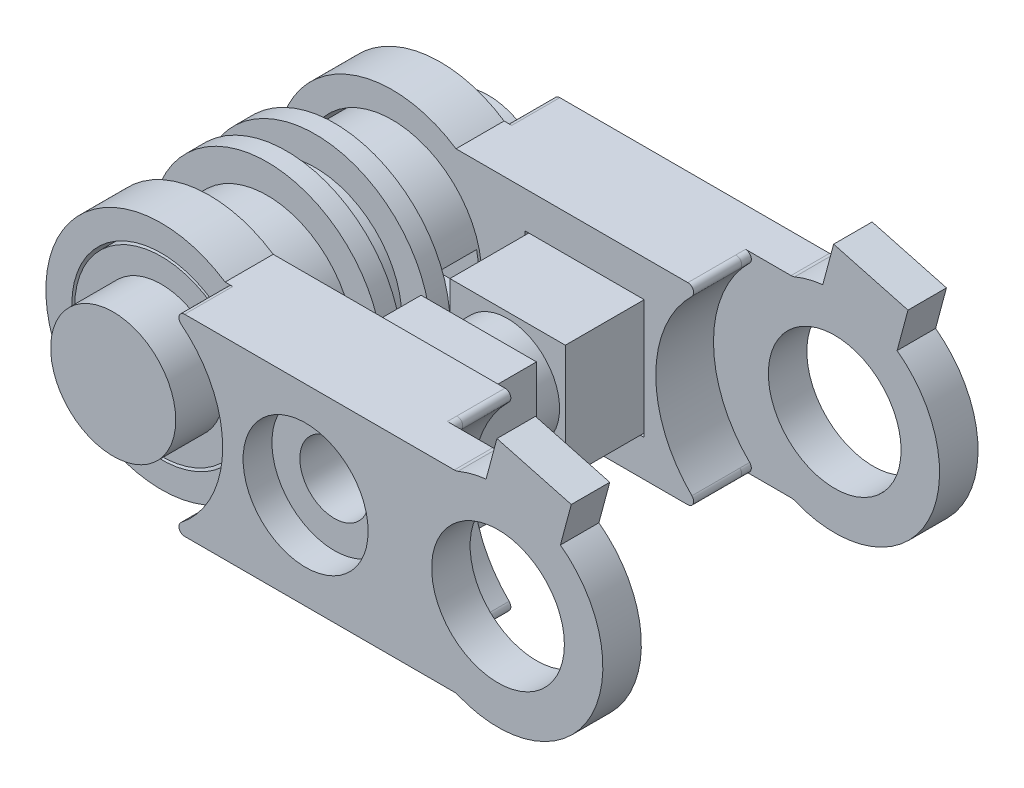
SolidWorks part; units mm, degrees
material "ABS"
ref_plane "正面" through (0, 0, 0) normal (0, 0, 1) x (1, 0, 0)
ref_plane "平面" through (0, 0, 0) normal (0, 1, 0) x (1, 0, 0)
ref_plane "右側面" through (0, 0, 0) normal (1, 0, 0) x (0, 0, -1)
sketch "ｽｹｯﾁ1" plane through (0, 0, 0) normal (0, 0, 1) x (1, 0, 0)
  circle A0 centre (0, 0) radius 4.5
  dimension "D1" = 9
extrude "ﾎﾞｽ - 押し出し1" add sketch "ｽｹｯﾁ1" along normal blind 3
sketch "ｽｹｯﾁ2" plane through (0, 0, 0) normal (0, 0, -1) x (-1, 0, 0)
  circle A0 centre (0, 0) radius 6
  dimension "D1" = 12
extrude "ﾎﾞｽ - 押し出し2" add sketch "ｽｹｯﾁ2" along normal blind 1
sketch "ｽｹｯﾁ3" plane through (0, 0, -1) normal (0, 0, -1) x (-1, 0, 0)
  circle A0 centre (0, 0) radius 4.5 construction
  circle A1 centre (0, 0) radius 4.5
extrude "ﾎﾞｽ - 押し出し3" add sketch "ｽｹｯﾁ3" along normal blind 1.5
sketch "ｽｹｯﾁ4" plane through (0, 0, -2.5) normal (0, 0, -1) x (-1, 0, 0)
  circle A1 centre (0, 0) radius 6
  circle A2 centre (0, 0) radius 6
  dimension "D1" = 0
extrude "ﾎﾞｽ - 押し出し4" add sketch "ｽｹｯﾁ4" along normal blind 1
sketch "ｽｹｯﾁ5" plane through (0, 0, -3.5) normal (0, 0, -1) x (-1, 0, 0)
  circle A0 centre (0, 0) radius 4.5 construction
  circle A1 centre (0, 0) radius 4.5
extrude "ﾎﾞｽ - 押し出し5" add sketch "ｽｹｯﾁ5" along normal blind 3
sketch "ｽｹｯﾁ6" plane through (0, 0, -6.5) normal (0, 0, -1) x (-1, 0, 0)
  circle A1 centre (0, 0) radius 6
  circle A2 centre (0, 0) radius 6
  dimension "D1" = 0
extrude "ﾎﾞｽ - 押し出し6" add sketch "ｽｹｯﾁ6" along normal blind 1
sketch "ｽｹｯﾁ7" plane through (0, 0, 3) normal (0, 0, 1) x (1, 0, 0)
  circle A1 centre (0, 0) radius 6
  circle A2 centre (0, 0) radius 6
  dimension "D1" = 0
extrude "ﾎﾞｽ - 押し出し7" add sketch "ｽｹｯﾁ7" along normal blind 1
sketch "ｽｹｯﾁ10" plane through (0, 0, 4) normal (0, 0, 1) x (1, 0, 0)
  line L1 (3.5, -3.5) -> (-3.5, -3.5) construction
  line L2 (3.5, -3.5) -> (3.5, 3.5) construction
  line L3 (3.5, 3.5) -> (-3.5, 3.5) construction
  line L4 (-3.5, -3.5) -> (-3.5, 3.5) construction
  line L5 (3.5, -3.5) -> (-3.5, 3.5) construction
  line L6 (3.5, 3.5) -> (-3.5, -3.5) construction
  circle A0 centre (0, 0) radius 4.25
  point P0 (0, 0)
  dimension "D3" = 8.5
  dimension "D1" = 7
  dimension "D2" = 7
extrude "ﾎﾞｽ - 押し出し10" add sketch "ｽｹｯﾁ10" along normal blind 1.5
sketch "ｽｹｯﾁ11" plane through (0, 0, 5.5) normal (0, 0, 1) x (1, 0, 0)
  circle A0 centre (0, 0) radius 3.25
  dimension "D1" = 6.5
extrude "ﾎﾞｽ - 押し出し11" add sketch "ｽｹｯﾁ11" along normal blind 2.5
ref_plane "平面1" through (0, 0, -1.75) normal (0, 0, 1) x (1, 0, 0)
mirror "ﾐﾗｰ1" about plane through (0, 0, -1.75) normal (0, 0, 1) of "ﾎﾞｽ - 押し出し11", "ﾎﾞｽ - 押し出し10"
sketch "ｽｹｯﾁ12" plane through (0, 0, 4) normal (0, 0, 1) x (1, 0, 0)
  line L0 (0, 0) -> (20, 0) construction
  line L1 (3.3166, 5) -> (16.1672, 5)
  line L3 (16.1672, -5) -> (3.3166, -5)
  circle A0 centre (0, 0) radius 6 construction
  circle A1 centre (20, 0) radius 3.45 construction
  arc A2 (3.3166, 5) -> (3.3166, -5) centre (0, 0) ccw
  circle A3 centre (20, 0) radius 5.45 construction
  circle A4 centre (20, 0) radius 6.3 construction
  arc A5 (16.1672, 5) -> (16.1672, -5) centre (20, 0) ccw
  circle A6 centre (20, 0) radius 6 construction
  circle A7 centre (0, 0) radius 6 construction
  circle A8 centre (20, 0) radius 3.25 construction
  circle A9 centre (0, 0) radius 3.25 construction
  circle A11 centre (0, 0) radius 4.39
  circle A12 centre (0, 0) radius 4.39
  dimension "D3" = 20
  dimension "D6" = 0.3
  dimension "D2" = 5
  dimension "D7" = 5
  dimension "D4" = 0.2
  dimension "D5" = 2
  dimension "D1" = 0.14
extrude "ﾎﾞｽ - 押し出し12" add sketch "ｽｹｯﾁ12" along normal blind 1.5 separate body
sketch "ｽｹｯﾁ13" plane through (0, 0, 5.5) normal (0, 0, 1) x (1, 0, 0)
  line L6 (16.1672, 5) -> (3.3166, 5) construction
  line L9 (16.1672, 5) -> (3.3166, 5) construction
  line L10 (15.3664, 5) -> (3.7135, 5)
  line L11 (15.3664, -5) -> (3.7135, -5)
  circle A1 centre (0, 0) radius 3.25 construction
  arc A7 (16.1672, 5) -> (16.1672, -5) centre (20, 0) ccw construction
  arc A8 (15.577, 4.4864) -> (15.577, -4.4864) centre (20, 0) ccw
  circle A10 centre (0, 0) radius 5.69 construction
  circle A11 centre (0, 0) radius 3.39 construction
  circle A12 centre (0, 0) radius 5.39 construction
  arc A13 (3.5275, 4.4646) -> (3.5275, -4.4646) centre (0, 0) cw
  arc A14 (15.3664, -5) -> (15.577, -4.4864) centre (15.3664, -4.7) ccw
  arc A15 (15.577, 4.4864) -> (15.3664, 5) centre (15.3664, 4.7) ccw
  arc A16 (3.7135, 5) -> (3.5275, 4.4646) centre (3.7135, 4.7) ccw
  arc A17 (3.5275, -4.4646) -> (3.7135, -5) centre (3.7135, -4.7) ccw
  point P24 (2.7159, 5)
  point P29 (2.7159, -5)
  dimension "D1" = 0.14
  dimension "D3" = 0.3
  dimension "D4" = 2
  dimension "D2" = 0.3
extrude "ﾎﾞｽ - 押し出し13" add sketch "ｽｹｯﾁ13" along normal blind 0.5
fillet "ﾌｨﾚｯﾄ9" radius 0.3 2 edges at (16.1672, -5, 4.75) (16.1672, 5, 4.75)
sketch "ｽｹｯﾁ14" plane through (0, 0, 6) normal (0, 0, 1) x (1, 0, 0)
  line L0 (3.7135, 5) -> (17.7301, 5)
  line L3 (3.7135, -5) -> (17.7301, -5)
  arc A0 (17.7301, 5) -> (17.9208, 5.0378) centre (17.7301, 5.5) ccw
  arc A1 (17.7301, -5) -> (17.9208, -5.0378) centre (17.7301, -5.5) cw
  arc A4 (3.5275, -4.4646) -> (3.7135, -5) centre (3.7135, -4.7) ccw construction
  arc A7 (3.5275, -4.4646) -> (3.5275, 4.4646) centre (0, 0) ccw construction
  arc A8 (3.7135, 5) -> (3.5275, 4.4646) centre (3.7135, 4.7) ccw construction
  arc A9 (3.5275, -4.4646) -> (3.7135, -5) centre (3.7135, -4.7) ccw
  arc A10 (3.7135, 5) -> (3.5275, 4.4646) centre (3.7135, 4.7) ccw
  arc A11 (3.5275, -4.4646) -> (3.5275, 4.4646) centre (0, 0) ccw
  circle A12 centre (20, 0) radius 5.45 construction
  arc A13 (17.9208, 5.0378) -> (17.9208, -5.0378) centre (20, 0) cw
  circle A14 centre (20, 0) radius 3.45 construction
  circle A15 centre (20, 0) radius 3.45
  point P19 (17.8315, -5)
  point P22 (17.8315, 5)
  point P24 (17.8315, 5)
  point P27 (17.8315, -5)
  dimension "D1" = 0.5
extrude "ﾎﾞｽ - 押し出し14" add sketch "ｽｹｯﾁ14" along normal blind 2
sketch "ｽｹｯﾁ15" plane through (0, 0, 4) normal (0, 0, -1) x (-1, 0, 0)
  line L0 (-15.3664, 5) -> (-4.1952, 5)
  line L1 (-3.3166, 5) -> (-16.1672, 5) construction
  line L2 (-15.3664, -5) -> (-4.1952, -5)
  line L3 (-16.1672, -5) -> (-3.3166, -5) construction
  circle A2 centre (0, 0) radius 6 construction
  arc A3 (-3.9955, 4.4762) -> (-3.9955, -4.4762) centre (0, 0) ccw
  arc A7 (-4.1952, -5) -> (-3.9955, -4.4762) centre (-4.1952, -4.7) ccw
  arc A8 (-4.1952, 5) -> (-3.9955, 4.4762) centre (-4.1952, 4.7) cw
  arc A10 (-15.577, -4.4864) -> (-15.3664, -5) centre (-15.3664, -4.7) ccw construction
  arc A11 (-15.577, -4.4864) -> (-15.577, 4.4864) centre (-20, 0) ccw construction
  arc A12 (-15.3664, 5) -> (-15.577, 4.4864) centre (-15.3664, 4.7) ccw construction
  arc A13 (-15.577, -4.4864) -> (-15.3664, -5) centre (-15.3664, -4.7) ccw
  arc A14 (-15.577, -4.4864) -> (-15.577, 4.4864) centre (-20, 0) ccw
  arc A15 (-15.3664, 5) -> (-15.577, 4.4864) centre (-15.3664, 4.7) ccw
  point P26 (-3.3166, -5)
  point P29 (-3.3166, 5)
  dimension "D2" = 0.3
extrude "ﾎﾞｽ - 押し出し15" add sketch "ｽｹｯﾁ15" along normal blind 1
mirror "ﾐﾗｰ2" about plane through (0, 0, -1.75) normal (0, 0, 1) of bodies 116
sketch "ｽｹｯﾁ16" plane through (0, 0, 8) normal (0, 0, 1) x (1, 0, 0)
  line L0 (0, 0) -> (20, 0) construction
  circle A0 centre (20, 0) radius 3.45 construction
  circle A1 centre (10, 0) radius 1.8
  dimension "D1" = 3.6
extrude "ｶｯﾄ - 押し出し1" cut sketch "ｽｹｯﾁ16" against normal through all
sketch "ｽｹｯﾁ17" plane through (0, 0, -6.5) normal (0, 0, 1) x (1, 0, 0)
  line L1 (13.1, -3.1) -> (6.9, -3.1)
  line L2 (13.1, -3.1) -> (13.1, 3.1)
  line L3 (13.1, 3.1) -> (6.9, 3.1)
  line L4 (6.9, -3.1) -> (6.9, 3.1)
  line L5 (13.1, -3.1) -> (6.9, 3.1) construction
  line L6 (13.1, 3.1) -> (6.9, -3.1) construction
  point P0 (10, 0)
  dimension "D2" = 6.2
  dimension "D1" = 6.2
extrude "ｶｯﾄ - 押し出し2" cut sketch "ｽｹｯﾁ17" against normal blind 2
sketch "ｽｹｯﾁ18" plane through (0, 0, 3) normal (0, 0, -1) x (-1, 0, 0)
  line L0 (-7, 3) -> (-13, 3)
  line L5 (-13, 3) -> (-13, -3)
  line L6 (-13, -3) -> (-7, -3)
  line L7 (-7, -3) -> (-7, 3)
  line L8 (-13.1, -3.1) -> (-6.9, -3.1)
  line L9 (-6.9, -3.1) -> (-6.9, 3.1)
  line L10 (-6.9, 3.1) -> (-13.1, 3.1)
  line L11 (-13.1, 3.1) -> (-13.1, -3.1)
  line L12 (-13.1, -3.1) -> (-6.9, -3.1) construction
  line L13 (-6.9, -3.1) -> (-6.9, 3.1) construction
  line L14 (-6.9, 3.1) -> (-13.1, 3.1) construction
  line L15 (-13.1, 3.1) -> (-13.1, -3.1) construction
  dimension "D1" = 0
  dimension "D2" = 0.1
extrude "ﾎﾞｽ - 押し出し16" add sketch "ｽｹｯﾁ18" along normal up to surface (11.5 mm away) up to face at (10, 0, -8.5)
sketch "ｽｹｯﾁ19" plane through (0, 0, 3) normal (0, 0, 1) x (1, 0, 0)
  circle A0 centre (10, 0) radius 1.8 construction
  circle A1 centre (10, 0) radius 1.8
extrude "ｶｯﾄ - 押し出し3" cut sketch "ｽｹｯﾁ19" against normal through all
sketch "ｽｹｯﾁ20" plane through (0, 0, -1.75) normal (0, 0, 1) x (1, 0, 0)
  line L4 (13, 3) -> (7, 3)
  line L5 (13, -3) -> (13, 3)
  line L6 (7, -3) -> (13, -3)
  line L7 (7, 3) -> (7, -3)
  line L8 (13, 3) -> (7, 3)
  line L9 (13, -3) -> (13, 3)
  line L10 (7, -3) -> (13, -3)
  line L11 (7, 3) -> (7, -3)
  circle A1 centre (10, 0) radius 2.7
  dimension "D2" = 5.4
  dimension "D1" = 0
extrude "ｶｯﾄ - 押し出し4" cut sketch "ｽｹｯﾁ20" against normal blind 0.75 and the other way blind 0.75
sketch "ｽｹｯﾁ21" plane through (0, 0, 8) normal (0, 0, 1) x (1, 0, 0)
  circle A0 centre (10, 0) radius 3.25
  dimension "D1" = 6.5
extrude "ｶｯﾄ - 押し出し5" cut sketch "ｽｹｯﾁ21" against normal blind 1.5
sketch "ｽｹｯﾁ22" plane through (0, 0, -11.5) normal (0, 0, -1) x (-1, 0, 0)
  line L1 (-11.6743, 2.9) -> (-13.3486, 0)
  line L2 (-13.3486, 0) -> (-11.6743, -2.9)
  line L3 (-11.6743, -2.9) -> (-8.3257, -2.9)
  line L4 (-8.3257, -2.9) -> (-6.6514, 0)
  line L5 (-6.6514, 0) -> (-8.3257, 2.9)
  line L6 (-8.3257, 2.9) -> (-11.6743, 2.9)
  circle A0 centre (-10, 0) radius 2.9 construction
  dimension "D1" = 5.8
extrude "ｶｯﾄ - 押し出し6" cut sketch "ｽｹｯﾁ22" against normal blind 1
sketch "ｽｹｯﾁ23" plane through (0, 0, 8) normal (0, 0, 1) x (1, 0, 0)
  line L0 (20, 0) -> (21.4106, 5.2643) construction
  line L1 (19.0128, 4.0433) -> (22.8765, 3.008)
  line L2 (19.0128, 4.0433) -> (19.9446, 7.5206)
  line L3 (19.9446, 7.5206) -> (23.8083, 6.4853)
  line L4 (22.8765, 3.008) -> (23.8083, 6.4853)
  line L5 (19.0128, 4.0433) -> (23.8083, 6.4853) construction
  line L6 (19.9446, 7.5206) -> (22.8765, 3.008) construction
  line L7 (20, 0) -> (20, 5.45) construction
  arc A0 (17.9208, -5.0378) -> (17.9208, 5.0378) centre (20, 0) ccw construction
  point P0 (21.4106, 5.2643)
  dimension "D1" = 1.8
  dimension "D2" = 4
  dimension "D3" = 15
extrude "ﾎﾞｽ - 押し出し17" add sketch "ｽｹｯﾁ23" against normal up to surface (2 mm away) up to face at (17.3986, 0, 6)
sketch "ｽｹｯﾁ24" plane through (0, 0, -11.5) normal (0, 0, -1) x (-1, 0, 0)
  line L4 (-22.8765, 3.008) -> (-19.0128, 4.0433)
  line L5 (-23.8083, 6.4853) -> (-22.8765, 3.008)
  line L6 (-19.9446, 7.5206) -> (-23.8083, 6.4853)
  line L7 (-19.0128, 4.0433) -> (-19.9446, 7.5206)
  line L8 (-22.8765, 3.008) -> (-19.0128, 4.0433)
  line L9 (-23.8083, 6.4853) -> (-22.8765, 3.008)
  line L10 (-19.9446, 7.5206) -> (-23.8083, 6.4853)
  line L11 (-19.0128, 4.0433) -> (-19.9446, 7.5206)
  dimension "D1" = 0
extrude "ﾎﾞｽ - 押し出し18" add sketch "ｽｹｯﾁ24" against normal up to surface (2 mm away) up to face at (17.3986, 0, -9.5)
ref_plane "平面2" through (-4.5, 0, 0) normal (-1, 0, 0) x (0, 0, 1)
sketch "ｽｹｯﾁ25" plane through (-4.5, 0, 0) normal (-1, 0, 0) x (0, 0, 1)
  line L0 (-6.5, 0) -> (3, 0) construction
  line L1 (-6.5, -4.5) -> (-6.5, 4.5) construction
  line L2 (3, 4.5) -> (3, -4.5) construction
  line L3 (-3.5, 4.5) -> (-3.5, -4.5) construction
  line L4 (-6.5, -1) -> (-3.5, -1)
  line L5 (-6.5, -1) -> (-6.5, 1)
  line L6 (-6.5, 1) -> (-3.5, 1)
  line L7 (-3.5, -1) -> (-3.5, 1)
  line L8 (0, -4.5) -> (0, 4.5) construction
  line L9 (0, -1) -> (3, -1)
  line L10 (0, -1) -> (0, 1)
  line L11 (0, 1) -> (3, 1)
  line L12 (3, -1) -> (3, 1)
  line L13 (3, 6) -> (3, -6) construction
  dimension "D1" = 2
sketch "ｽｹｯﾁ26" plane through (0, 0, 3) normal (0, 0, -1) x (-1, 0, 0)
  circle A2 centre (0, 0) radius 5.8
  circle A3 centre (0, 0) radius 5.8
  circle A4 centre (0, 0) radius 6
  circle A5 centre (0, 0) radius 6
  dimension "D1" = 0.2
  dimension "D2" = 0
extrude "ｶｯﾄ - 押し出し8" cut sketch "ｽｹｯﾁ26" against normal through all
sketch "ｽｹｯﾁ27" plane through (0, 0, -6.5) normal (0, 0, 1) x (1, 0, 0)
  circle A1 centre (0, 0) radius 6
  circle A2 centre (0, 0) radius 6
  circle A3 centre (0, 0) radius 5.8
  circle A4 centre (0, 0) radius 5.8
  dimension "D1" = 0
  dimension "D2" = 0
extrude "ｶｯﾄ - 押し出し9" cut sketch "ｽｹｯﾁ27" against normal through all
sketch "ｽｹｯﾁ28" plane through (0, 0, 4) normal (0, 0, -1) x (-1, 0, 0)
  circle A0 centre (0, 0) radius 4.25 construction
  circle A1 centre (0, 0) radius 5.8
  circle A2 centre (0, 0) radius 5.8
  circle A3 centre (0, 0) radius 4.25
  dimension "D1" = 0
extrude "ｶｯﾄ - 押し出し10" cut sketch "ｽｹｯﾁ28" along normal blind 1
sketch "ｽｹｯﾁ29" plane through (0, 0, -7.5) normal (0, 0, 1) x (1, 0, 0)
  circle A1 centre (0, 0) radius 4.25
  circle A2 centre (0, 0) radius 4.25
  circle A3 centre (0, 0) radius 5.8
  circle A4 centre (0, 0) radius 5.8
  dimension "D1" = 0
  dimension "D2" = 0
extrude "ｶｯﾄ - 押し出し11" cut sketch "ｽｹｯﾁ29" along normal blind 1
sketch "ｽｹｯﾁ30" plane through (0, 0, 4) normal (0, 0, -1) x (-1, 0, 0)
  line L2 (-4.1952, -5) -> (-3.3166, -5)
  line L3 (-3.3166, 5) -> (-4.1952, 5)
  line L4 (-4.1952, -5) -> (-3.3166, -5)
  line L5 (-3.3166, 5) -> (-4.1952, 5)
  circle A0 centre (0, 0) radius 4.39 construction
  circle A1 centre (0, 0) radius 4.39
  arc A4 (-3.9955, 4.4762) -> (-4.1952, 5) centre (-4.1952, 4.7) ccw
  arc A5 (-3.9955, 4.4762) -> (-3.9955, -4.4762) centre (0, 0) ccw
  arc A6 (-4.1952, -5) -> (-3.9955, -4.4762) centre (-4.1952, -4.7) ccw
  arc A7 (-3.3166, -5) -> (-3.3166, 5) centre (0, 0) ccw
  arc A8 (-3.9955, 4.4762) -> (-4.1952, 5) centre (-4.1952, 4.7) ccw
  arc A9 (-3.9955, 4.4762) -> (-3.9955, -4.4762) centre (0, 0) ccw
  arc A10 (-4.1952, -5) -> (-3.9955, -4.4762) centre (-4.1952, -4.7) ccw
  arc A11 (-3.3166, -5) -> (-3.3166, 5) centre (0, 0) ccw
  dimension "D1" = 0
extrude "ﾎﾞｽ - 押し出し19" add sketch "ｽｹｯﾁ30" along normal blind 1
sketch "ｽｹｯﾁ31" plane through (0, 0, -7.5) normal (0, 0, 1) x (1, 0, 0)
  line L2 (3.3166, -5) -> (4.1952, -5)
  line L3 (4.1952, 5) -> (3.3166, 5)
  line L4 (3.3166, -5) -> (4.1952, -5)
  line L5 (4.1952, 5) -> (3.3166, 5)
  circle A1 centre (0, 0) radius 4.39
  circle A2 centre (0, 0) radius 4.39
  arc A6 (3.3166, 5) -> (3.3166, -5) centre (0, 0) ccw
  arc A7 (4.1952, 5) -> (3.9955, 4.4762) centre (4.1952, 4.7) ccw
  arc A8 (3.9955, -4.4762) -> (3.9955, 4.4762) centre (0, 0) ccw
  arc A9 (3.9955, -4.4762) -> (4.1952, -5) centre (4.1952, -4.7) ccw
  arc A10 (3.3166, 5) -> (3.3166, -5) centre (0, 0) ccw
  arc A11 (4.1952, 5) -> (3.9955, 4.4762) centre (4.1952, 4.7) ccw
  arc A12 (3.9955, -4.4762) -> (3.9955, 4.4762) centre (0, 0) ccw
  arc A13 (3.9955, -4.4762) -> (4.1952, -5) centre (4.1952, -4.7) ccw
  dimension "D1" = 0
  dimension "D2" = 0
extrude "ﾎﾞｽ - 押し出し20" add sketch "ｽｹｯﾁ31" along normal blind 1
sketch "ｽｹｯﾁ32" plane through (0, 0, 5.5) normal (0, 0, 1) x (1, 0, 0)
  circle A0 centre (0, 0) radius 4.65
  dimension "D1" = 9.3
extrude "ｶｯﾄ - 押し出し12" cut sketch "ｽｹｯﾁ32" against normal through all
sketch "ｽｹｯﾁ33" plane through (0, 0, 3) normal (0, 0, 1) x (1, 0, 0)
  circle A0 centre (0, 0) radius 4.25 construction
  circle A1 centre (0, 0) radius 4.5
  circle A2 centre (0, 0) radius 4.5
  circle A3 centre (0, 0) radius 4.25
  dimension "D1" = 0
extrude "ﾎﾞｽ - 押し出し21" add sketch "ｽｹｯﾁ33" along normal up to surface (2.5 mm away) up to face at (3.25, 0, 5.5)
sketch "ｽｹｯﾁ34" plane through (0, 0, -6.5) normal (0, 0, -1) x (-1, 0, 0)
  circle A1 centre (0, 0) radius 4.25
  circle A2 centre (0, 0) radius 4.25
  circle A3 centre (0, 0) radius 4.5
  circle A4 centre (0, 0) radius 4.5
  dimension "D1" = 0
  dimension "D2" = 0
extrude "ﾎﾞｽ - 押し出し22" add sketch "ｽｹｯﾁ34" along normal up to surface (2.5 mm away) up to face at (3.25, 0, -9)
extrude "ｶｯﾄ - 押し出し13" cut sketch "ｽｹｯﾁ25" against normal through all
equation "\"D7@ｽｹｯﾁ12\"=\"D2@ｽｹｯﾁ12\""
equation "\"D1@ｽｹｯﾁ17\"=\"D2@ｽｹｯﾁ17\""
equation "\"D2@ｽｹｯﾁ25\"=\"D1@ｽｹｯﾁ25\"/2"
